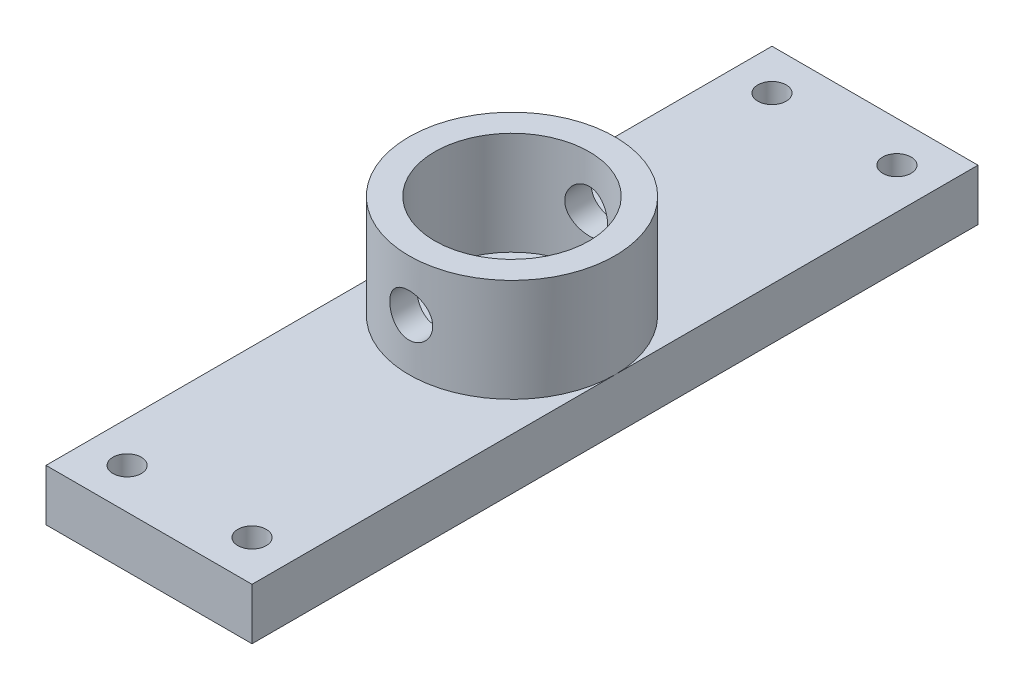
SolidWorks part; units mm, degrees
ref_plane "Front Plane" through (0, 0, 0) normal (0, 0, 1) x (1, 0, 0)
ref_plane "Top Plane" through (0, 0, 0) normal (0, 1, 0) x (1, 0, 0)
ref_plane "Right Plane" through (0, 0, 0) normal (1, 0, 0) x (0, 0, -1)
sketch "Sketch1" plane through (0, 0, 0) normal (0, 1, 0) x (1, 0, 0)
  line L1 (0, 0) -> (25.4, 0)
  line L2 (0, 0) -> (0, 89.5)
  line L3 (0, 89.5) -> (25.4, 89.5)
  line L4 (25.4, 0) -> (25.4, 89.5)
  circle A0 centre (5, 84.5) radius 1.75
  circle A1 centre (20.4, 84.5) radius 1.75
  circle A2 centre (5, 5) radius 1.75
  circle A3 centre (20.4, 5) radius 1.75
  dimension "D3" = 3.5
  dimension "D1" = 89.5
  dimension "D2" = 25.4
  dimension "D4" = 5
  dimension "D5" = 5
  dimension "D6" = 5
  dimension "D7" = 5
extrude "Boss-Extrude1" add sketch "Sketch1" along normal blind 6.35
sketch "Sketch2" plane through (0, 6.35, 0) normal (0, 1, 0) x (1, 0, 0)
  line L1 (25.4, 89.5) -> (0, 89.5) construction
  circle A0 centre (12.7, 44.75) radius 12.7
  circle A1 centre (12.7, 44.75) radius 9.525
  point P2 (12.7, 89.5)
  dimension "D1" = 44.75
  dimension "D2" = 25.4
  dimension "D3" = 19.05
extrude "Boss-Extrude2" add sketch "Sketch2" along normal blind 12.7
sketch "Sketch3" plane through (0, 0, 0) normal (1, 0, 0) x (0, 0, -1)
  line L1 (0, 6.35) -> (0, 0) construction
  line L3 (57.45, 19.05) -> (32.05, 19.05) construction
  circle A0 centre (36.75, 12.7) radius 2.5
  dimension "D1" = 36.75
  dimension "D3" = 5
  dimension "D2" = 6.35
ref_plane "Plane1" through (0, 0, -32.05) normal (0, 0, 1) x (0, -1, 0)
sketch "Sketch4" plane through (0, 0, -32.05) normal (0, 0, 1) x (0, -1, 0)
  line L0 (-6.35, 25.4) -> (-19.05, 25.4) construction
  line L2 (-6.35, 0) -> (-6.35, 25.4) construction
  circle A0 centre (-12.7, 12.7) radius 2.65
  dimension "D1" = 12.7
  dimension "D3" = 5.3
  dimension "D2" = 6.35
extrude "Cut-Extrude2" cut sketch "Sketch4" against normal blind 33.02
